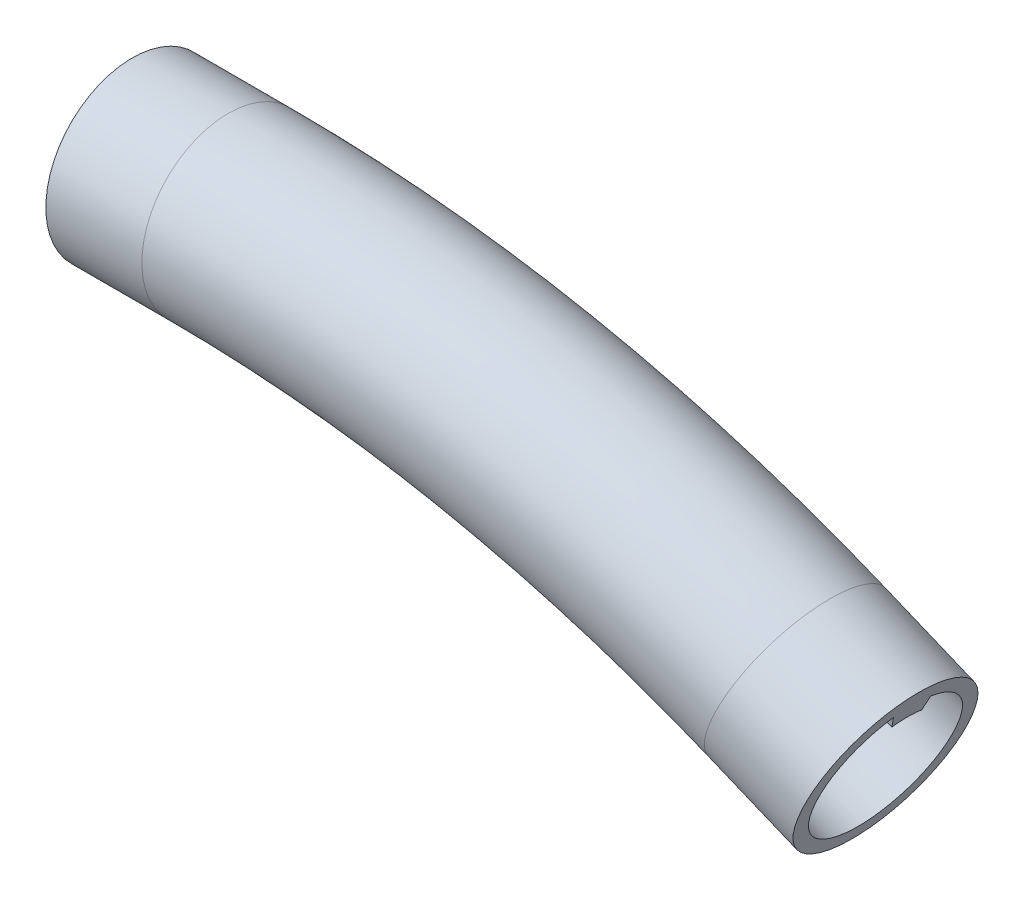
SolidWorks part; units mm, degrees
ref_plane "Front" through (0, 0, 0) normal (0, 0, 1) x (1, 0, 0)
ref_plane "Top" through (0, 0, 0) normal (0, 1, 0) x (1, 0, 0)
ref_plane "Right" through (0, 0, 0) normal (1, 0, 0) x (0, 0, -1)
sketch "Sketch2path" plane through (0, 0, 0) normal (0, 0, 1) x (1, 0, 0)
  line L0 (69.224, 88.2196) -> (78.4628, 84.3928)
  line L2 (10, 100) -> (0, 100)
  arc A1 (10, 100) -> (69.224, 88.2196) centre (10, -54.7598) cw
  dimension "D1" = 10
  dimension "D2" = 10
  dimension "D3" = 22.5
  dimension "D4" = 80
sketch "Sketch3" plane through (0, 0, 0) normal (1, 0, 0) x (0, 0, -1)
  circle A0 centre (0, 100) radius 9
  circle A1 centre (0, 100) radius 7.5
  dimension "D1" = 1.5
  dimension "D2" = 18
  dimension "D3" = 100
sweep "Sweep1" add profiles "Sketch3" path "Sketch2path"
ref_point "Point1"
ref_point "Point2"
ref_axis "Axis1" through (78.4628, 84.3928, 0) along (0, 0, 1)
ref_axis "Axis2" through (0, 100, 0) along (0, 0, 1)
ref_axis "Axis3" through (10, 100, 0) along (-1, 0, 0)
ref_axis "Axis4" through (70.577, 87.6592, 0) along (0.9239, -0.3827, 0)
ref_plane "Plane1" through (32.5155, -13.4683, 0) normal (0.9239, -0.3827, 0) x (0, 0, -1)
sketch "Sketch4" plane through (32.5155, -13.4683, 0) normal (0.9239, -0.3827, 0) x (0, 0, -1)
  line L2 (4.7631, 110.7452) -> (5.6292, 111.2452)
  line L3 (5.5, 107.9952) -> (6.5, 107.9952)
  arc A0 (6.5, 107.9952) -> (5.6292, 111.2452) centre (0, 107.9952) ccw
  arc A1 (5.5, 107.9952) -> (4.7631, 110.7452) centre (0, 107.9952) ccw
  dimension "D3" = 4.7631
  dimension "D4" = 107.9952
  dimension "D1" = 6.5
  dimension "D2" = 5.5
extrude "Boss-Extrude1" [suppressed] add sketch "Sketch4" against normal blind 5 contours A0 L2 A1 L3
ref_plane "Plane2" through (5, 0, 0) normal (-1, 0, 0) x (0, 0, 1)
sketch "Sketch6" plane through (5, 0, 5) normal (1, 0, 0) x (0, 0, -1)
  line L2 (0.2369, 97.25) -> (-0.6292, 96.75)
  line L3 (-0.5, 100) -> (-1.5, 100)
  arc A0 (-1.5, 100) -> (-0.6292, 96.75) centre (5, 100) ccw
  arc A1 (-0.5, 100) -> (0.2369, 97.25) centre (5, 100) ccw
  dimension "D3" = 4.7631
  dimension "D4" = 96.75
  dimension "D1" = 6.5
  dimension "D2" = 5.5
extrude "Boss-Extrude2" [suppressed] add sketch "Sketch6" along normal blind 5 contours A1 L2 A0 L3
ref_plane "Plane3" [suppressed] through (0, 0, 9) normal (0, 0, 1) x (1, 0, 0)
sketch "Sketch7" [suppressed] plane through (0, 0, 9) normal (0, 0, 1) x (1, 0, 0)
  line L1 (0, 100) -> (3, 100)
  line L2 (0, 100) -> (0, 99.5)
  line L3 (0, 99.5) -> (3, 99.5)
  line L4 (3, 100) -> (3, 99.5)
  dimension "D1" = 3
  dimension "D2" = 0.5
revolve "Cut-Revolve1" [suppressed] cut sketch "Sketch7" angle 360 about L1
sketch "Sketch8" [suppressed] plane through (0, 0, 9) normal (0, 0, 1) x (1, 0, 0)
  line L0 (78.4628, 84.3928) -> (75.6912, 85.5408)
  line L1 (70.577, 87.6592) -> (88.6536, 80.1716) construction
  line L2 (75.6912, 85.5408) -> (75.4998, 85.0789)
  line L3 (75.4998, 85.0789) -> (78.2715, 83.9308)
  line L4 (75.0187, 76.0779) -> (81.907, 92.7077) construction
  line L5 (78.2715, 83.9308) -> (78.4628, 84.3928)
  dimension "D1" = 3
  dimension "D2" = 0.5
revolve "Cut-Revolve2" [suppressed] cut sketch "Sketch8" angle 360 about L0
sketch "Sketch9" plane through (37.1349, -15.3818, 0) normal (0.9239, -0.3827, 0) x (0, 0, -1)
  line L0 (0, 107.9952) -> (-7.9816, 107.9952) construction
  line L1 (-1.5529, 113.7907) -> (-1.9411, 115.2396)
  line L3 (1.9411, 115.2396) -> (1.5529, 113.7907)
  line L4 (-1.6676, 113.8108) -> (-2.0811, 115.2527) construction
  arc A0 (1.9411, 115.2396) -> (-1.9411, 115.2396) centre (0, 107.9952) ccw
  arc A1 (1.5529, 113.7907) -> (-1.5529, 113.7907) centre (0, 107.9952) ccw
  circle A3 centre (0, 107.9952) radius 7.5 construction
  dimension "D1" = 1.5
  dimension "D2" = 30
  dimension "D3" = 1
extrude "Boss-Extrude3" add sketch "Sketch9" against normal blind 5
sketch "Sketch10" plane through (0, 0, 0) normal (-1, 0, 0) x (0, 0, 1)
  line L0 (-1.5529, 105.7956) -> (-1.9411, 107.2444)
  line L2 (1.9411, 107.2444) -> (1.5529, 105.7956)
  line L3 (-1.6676, 105.8156) -> (-2.0811, 107.2575) construction
  arc A0 (1.9411, 107.2444) -> (-1.9411, 107.2444) centre (0, 100) ccw
  arc A1 (1.5529, 105.7956) -> (-1.5529, 105.7956) centre (0, 100) ccw
  circle A2 centre (0, 100) radius 7.5 construction
  dimension "D1" = 1.5
  dimension "D2" = 30
  dimension "D3" = 1
extrude "Boss-Extrude4" add sketch "Sketch10" against normal blind 5
sketch "Sketch12" plane through (0, 0, 0) normal (0, 0, 1) x (1, 0, 0)
  line L0 (12.57, 92.4776) -> (12.6049, 94.4773)
  line L1 (16.4234, 92.3598) -> (16.5106, 94.3579)
  line L2 (63.9709, 82.2533) -> (64.7039, 84.1141)
  line L3 (60.3658, 83.6191) -> (61.0499, 85.4985)
  line L6 (39.5421, 104.788) -> (39.1779, 102.8215)
  line L7 (43.7084, 103.96) -> (43.2929, 102.0037)
  arc A2 (43.2929, 102.0037) -> (39.1779, 102.8215) centre (10, -54.7598) ccw
  arc A6 (63.9709, 82.2533) -> (60.3658, 83.6191) centre (10, -54.7598) ccw
  arc A9 (64.7039, 84.1141) -> (61.0499, 85.4985) centre (10, -54.7598) ccw
  arc A10 (16.4234, 92.3598) -> (12.57, 92.4776) centre (10, -54.7598) ccw
  arc A12 (16.5106, 94.3579) -> (12.6049, 94.4773) centre (10, -54.7598) ccw
  arc A15 (43.7084, 103.96) -> (39.5421, 104.788) centre (10, -54.7598) ccw
  dimension "D8" = 43.2929
  dimension "D5" = 12.6049
  dimension "D9" = 60.3658
  dimension "D10" = 84.1141
  dimension "D1" = 160.2598
  dimension "D2" = 147.2598
  dimension "D3" = 149.2598
  dimension "D4" = 12.57
  dimension "D6" = 16.4234
  dimension "D7" = 39.1779
  dimension "D11" = 92.4776
extrude "Boss-Extrude5" add sketch "Sketch12" along normal up to body and the other way up to body
ref_plane "Plane4 polowki" through (0, 0, 0) normal (0, 0, 1) x (1, 0, 0)
other "SurfaceCut1lewa" [suppressed]
other "SurfaceCut2prawa" [suppressed]
